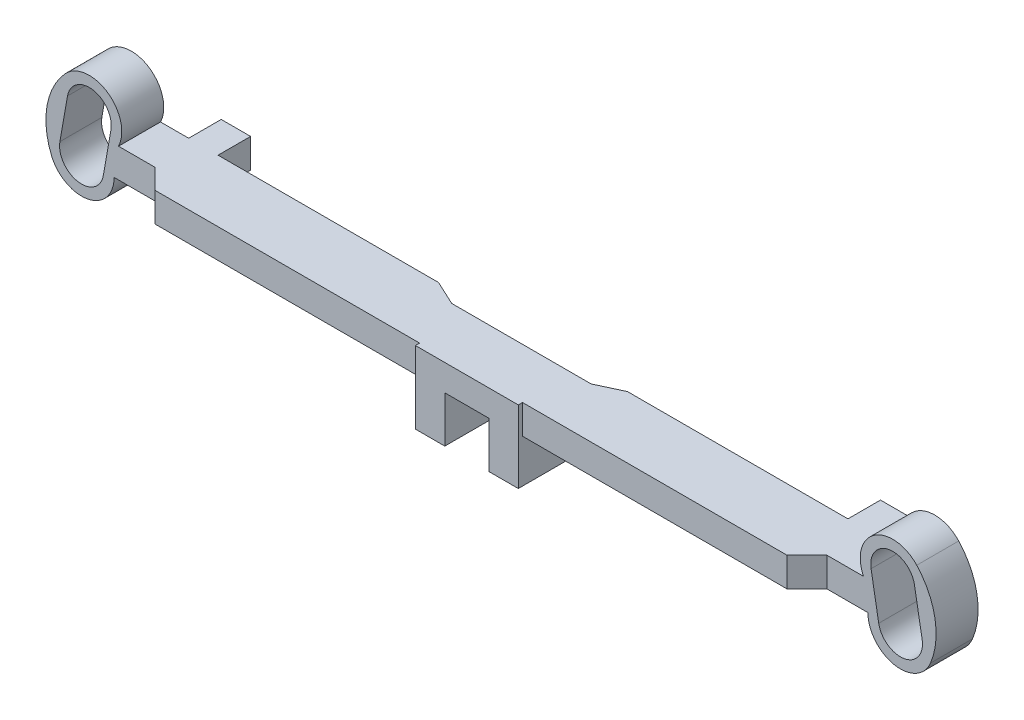
SolidWorks part; units mm, degrees
ref_plane "Plan de face" through (0, 0, 0) normal (0, 0, 1) x (1, 0, 0)
ref_plane "Plan de dessus" through (0, 0, 0) normal (0, 1, 0) x (1, 0, 0)
ref_plane "Plan de droite" through (0, 0, 0) normal (1, 0, 0) x (0, 0, -1)
sketch "Esquisse1" plane through (0, 0, 0) normal (0, 0, 1) x (1, 0, 0)
  line L0 (-19.5, 0) -> (19.5, 0) construction
  line L1 (-19.5, 0) -> (-19.1353, 2.0681) construction
  line L2 (-17.95, 0) -> (17.95, 0)
  line L3 (0, 0) -> (0, 7.0728) construction
  line L4 (17.7409, 1.3913) -> (-17.7409, 1.3913)
  line L5 (-20.534, 0.1823) -> (-20.1694, 2.2504)
  line L6 (-18.466, -0.1823) -> (-18.1013, 1.8858)
  line L7 (18.466, -0.1823) -> (18.1013, 1.8858)
  line L8 (20.534, 0.1823) -> (20.1694, 2.2504)
  arc A0 (-20.534, 0.1823) -> (-18.466, -0.1823) centre (-19.5, 0) ccw
  arc A1 (20.534, 0.1823) -> (18.466, -0.1823) centre (19.5, 0) cw
  arc A2 (-18.1013, 1.8858) -> (-20.1694, 2.2504) centre (-19.1353, 2.0681) ccw
  arc A3 (18.1013, 1.8858) -> (20.1694, 2.2504) centre (19.1353, 2.0681) cw
  arc A8 (-20.9312, -0.5951) -> (-17.95, 0) centre (-19.5, 0) ccw
  arc A9 (-20.9312, -0.5951) -> (-20.2767, 3.1168) centre (-17.6995, 0.7487) cw
  arc A10 (-17.7409, 1.3913) -> (-20.2767, 3.1168) centre (-19.1353, 2.0681) ccw
  arc A12 (17.7409, 1.3913) -> (20.2767, 3.1168) centre (19.1353, 2.0681) cw
  arc A13 (20.9312, -0.5951) -> (20.2767, 3.1168) centre (17.6995, 0.7487) ccw
  arc A14 (20.9312, -0.5951) -> (17.95, 0) centre (19.5, 0) cw
  point P4 (0, 0)
  point P22 (-17.7, 0.0037)
  point P26 (-17.3468, 0.9742)
  point P31 (17.3468, 0.9742)
  point P36 (17.7, 0.0037)
  dimension "D1" = 2.1
  dimension "D7" = 3.5
  dimension "D8" = 1.55
  dimension "D5" = 1.55
  dimension "D6" = 1.55
  dimension "D9" = 1.55
  dimension "D10" = 3.5
  dimension "D2" = 39
  dimension "D3" = 2.1
  dimension "D4" = 80
  dimension "D11" = 35.4819
extrude "Boss.-Extru.1" add sketch "Esquisse1" along normal blind 2
sketch "Esquisse2" plane through (0, 0, 0) normal (0, -1, 0) x (1, 0, 0)
  line L0 (-16, 2) -> (-15.05, 2.95)
  line L1 (-17.95, 2) -> (17.95, 2) construction
  line L2 (-15.05, 2.95) -> (15.05, 2.95)
  line L3 (15.05, 2.95) -> (16, 2)
  line L4 (16, 2) -> (-16, 2)
  line L6 (-17.95, 0) -> (17.95, 0) construction
  point P6 (0, 2.95)
  point P9 (0, 2)
  dimension "D1" = 45
  dimension "D2" = 32
  dimension "D3" = 2.95
extrude "Boss.-Extru.2" add sketch "Esquisse2" against normal up to surface (1.3913 mm away) up to face at (0, 1.3913, 1)
sketch "Esquisse3" plane through (0, 0, 0) normal (0, -1, 0) x (1, 0, 0)
  line L0 (-4.5, 0) -> (-3.3205, 0.55)
  line L1 (-17.95, 0) -> (17.95, 0) construction
  line L2 (-3.3205, 0.55) -> (3.3205, 0.55)
  line L3 (3.3205, 0.55) -> (4.5, 0)
  line L4 (4.5, 0) -> (-4.5, 0)
  line L5 (15.05, 2.95) -> (-15.05, 2.95) construction
  point P4 (0, 0.55)
  point P7 (0, 0)
  dimension "D1" = 25
  dimension "D2" = 9
  dimension "D3" = 2.4
extrude "Enlèv. mat.-Extru.1" cut sketch "Esquisse3" against normal blind 2
sketch "Esquisse4" plane through (0, 0, 2.95) normal (0, 0, 1) x (1, 0, 0)
  line L1 (-2.45, -2.0587) -> (2.45, -2.0587)
  line L2 (-2.45, -2.0587) -> (-2.45, 1.3913)
  line L3 (-2.45, 1.3913) -> (2.45, 1.3913)
  line L4 (2.45, -2.0587) -> (2.45, 1.3913)
  line L6 (3.3205, 1.3913) -> (-3.3205, 1.3913) construction
  point P6 (0, 1.3913)
  dimension "D1" = 4.9
  dimension "D2" = 3.45
extrude "Boss.-Extru.3" add sketch "Esquisse4" against normal up to surface (2.4 mm away) and the other way blind 0.2 up to face at (0, 0.6956, 0.55)
sketch "Esquisse5" plane through (0, 0, 3.15) normal (0, 0, 1) x (1, 0, 0)
  line L1 (-1.05, 0.1413) -> (1.05, 0.1413)
  line L2 (-1.05, 0.1413) -> (-1.05, -2.0587)
  line L3 (-1.05, -2.0587) -> (1.05, -2.0587)
  line L4 (1.05, 0.1413) -> (1.05, -2.0587)
  line L5 (-2.45, -2.0587) -> (2.45, -2.0587) construction
  point P6 (0, -2.0587)
  dimension "D1" = 2.2
  dimension "D2" = 2.1
extrude "Enlèv. mat.-Extru.2" cut sketch "Esquisse5" against normal blind 4
sketch "Esquisse6" plane through (0, 1.3913, 0) normal (0, 1, 0) x (1, 0, 0)
  line L0 (-4.5, 0) -> (-17.7409, 0) construction
  line L1 (-16.4, 0) -> (-15, 0)
  line L2 (-16.4, 0) -> (-16.4, 1.55)
  line L3 (-16.4, 1.55) -> (-15, 1.55)
  line L4 (-15, 0) -> (-15, 1.55)
  line L5 (17.7409, 0) -> (4.5, 0) construction
  line L6 (15, 0) -> (16.4, 0)
  line L7 (15, 0) -> (15, 1.55)
  line L8 (15, 1.55) -> (16.4, 1.55)
  line L9 (16.4, 0) -> (16.4, 1.55)
  line L10 (-15, 1.55) -> (15, 1.55) construction
  point P12 (0, 1.55)
  dimension "D1" = 1.4
  dimension "D2" = 32.8
  dimension "D3" = 1.55
extrude "Boss.-Extru.4" add sketch "Esquisse6" against normal up to surface (1.3913 mm away) up to face at (-10.0213, 0, 1.4344)
scale "Scale1" scale about centroid uniform scaling yes scale factor 6.5
